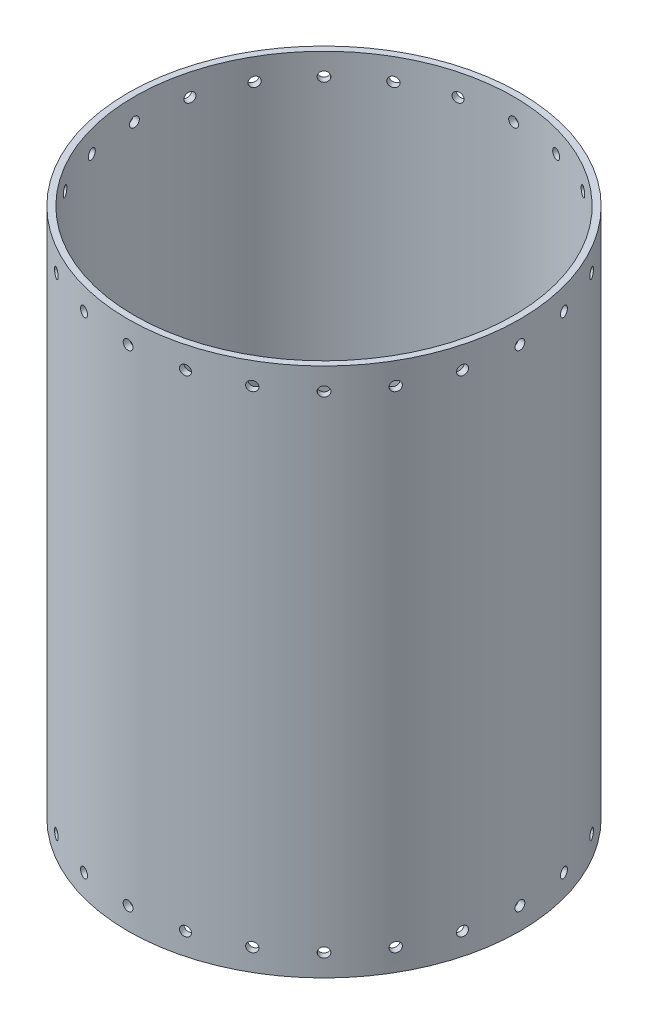
SolidWorks part; units mm, degrees
ref_plane "Front Plane" through (0, 0, 0) normal (0, 0, 1) x (1, 0, 0)
ref_plane "Top Plane" through (0, 0, 0) normal (0, 1, 0) x (1, 0, 0)
ref_plane "Right Plane" through (0, 0, 0) normal (1, 0, 0) x (0, 0, -1)
sketch "Sketch1" plane through (0, 0, 0) normal (0, 1, 0) x (1, 0, 0)
  circle A0 centre (0, 0) radius 98.425
  dimension "D1" = 196.85
extrude "Extrude-Thin1" add sketch "Sketch1" along normal blind 275.082 thin thin type one direction wall 3.302
ref_plane "Plane1" through (0, 263.652, 0) normal (0, 1, 0) x (1, 0, 0)
sketch "Sketch2" plane through (0, 263.652, 0) normal (0, 1, 0) x (1, 0, 0)
  line L0 (0, 0) -> (0, -116.6708) construction
  line L2 (0, -93.98) -> (2.54, -93.98)
  line L3 (0, -93.98) -> (0, -106.68)
  line L4 (0, -106.68) -> (2.54, -106.68)
  line L5 (2.54, -93.98) -> (2.54, -106.68)
  point P7 (-2.54, -93.98)
  point P8 (-1.3491, -93.6499)
  point P9 (2.6467, -93.5706)
  dimension "D1" = 12.7
  dimension "D2" = 5.08
  dimension "D3" = 2.54
  dimension "D4" = 93.98
revolve "Cut-Revolve1" cut sketch "Sketch2" angle 360 about L0
sketch "Sketch3" plane through (0, 0, 0) normal (0, 0, 1) x (1, 0, 0)
  line L0 (0, 0) -> (0, 275.082) construction
  line L1 (98.425, 275.082) -> (-98.425, 275.082) construction
pattern_circular "CirPattern1" count 24 over 360 about axis through (0, 0, 0) along (0, 1, 0) of "Cut-Revolve1" reverse direction yes
ref_plane "Plane2" through (0, 137.541, 0) normal (0, 1, 0) x (1, 0, 0)
mirror "Mirror1" about plane through (0, 137.541, 0) normal (0, 1, 0) of "CirPattern1"
